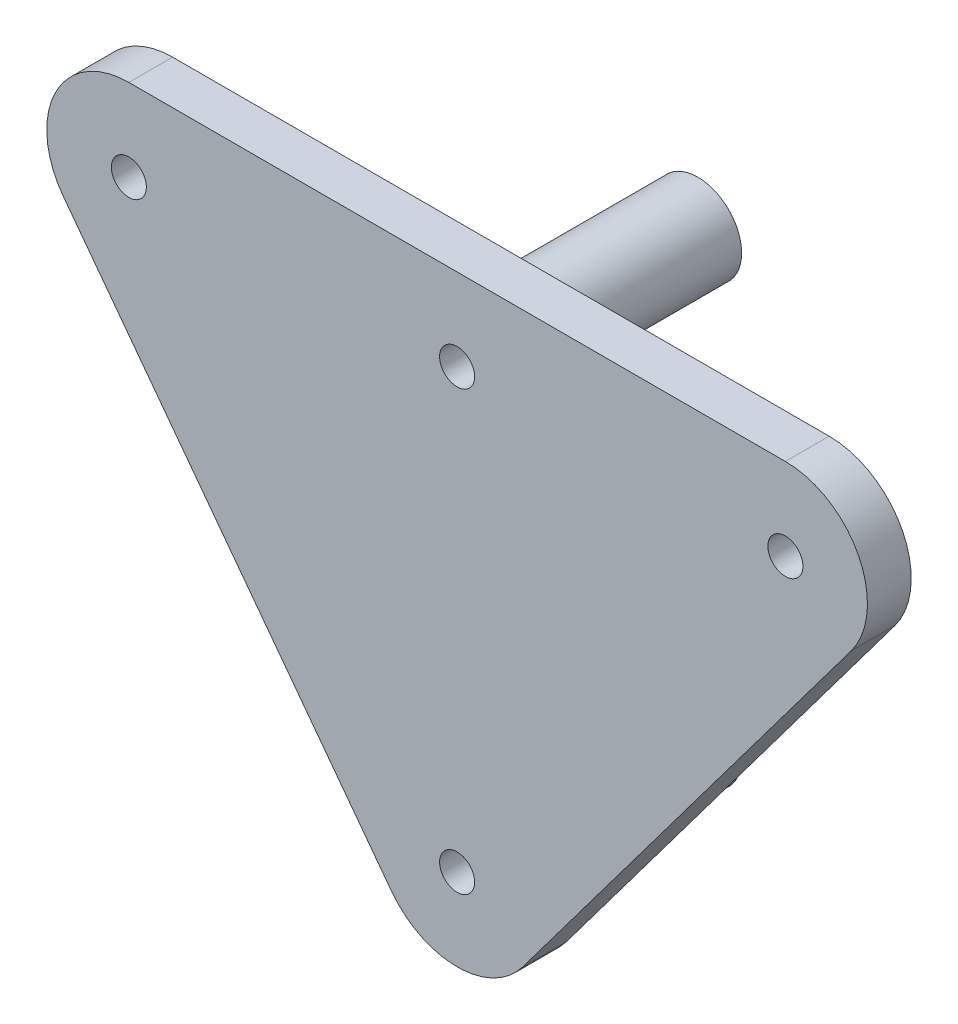
SolidWorks part; units mm, degrees
ref_plane "Front Plane" through (0, 0, 0) normal (0, 0, 1) x (1, 0, 0)
ref_plane "Top Plane" through (0, 0, 0) normal (0, 1, 0) x (1, 0, 0)
ref_plane "Right Plane" through (0, 0, 0) normal (1, 0, 0) x (0, 0, -1)
ref_axis "X" through (-88.99, 0, 0) along (1, 0, 0)
ref_axis "Y" through (0, 55, 0) along (0, -1, 0)
ref_axis "Z" through (0, 0, -88.99) along (0, 0, 1)
sketch "Sketch1" plane through (0, 0, 0) normal (0, 0, 1) x (1, 0, 0)
  line L0 (-36, 15.5) -> (-6, -24.5)
  line L1 (6, -24.5) -> (36, 15.5)
  line L2 (-30, 27.5) -> (30, 27.5)
  circle A0 centre (-30, 20) radius 7.5
  circle A1 centre (30, 20) radius 7.5
  circle A2 centre (0, -20) radius 7.5
  circle A3 centre (0, 20) radius 7.5
  circle A4 centre (0, 20) radius 4
  circle A5 centre (0, -20) radius 4
  circle A6 centre (-30, 20) radius 1.6
  circle A7 centre (0, 20) radius 1.6
  circle A8 centre (0, -20) radius 1.6
  circle A9 centre (30, 20) radius 1.6
  dimension "D1" = 15
  dimension "D2" = 8
  dimension "D3" = 3.2
extrude "Boss-Extrude1" add sketch "Sketch1" along normal blind 4 contours A0 | L2 A3 A0 L0 A2 L1 A1 | A1 | A2 A5 | A3 A4 | A4 | A5 region at (5.1533, 25.1533, 0) region at (0, 6.0857, 0) region at (-36.5185, 23.2592, 0) region at (-2.3046, -13.0861, 0) region at (23.4815, 16.7408, 0) region at (-3.8869, 20, 0) region at (-3.8869, -20, 0)
extrude "Boss-Extrude2" add sketch "Sketch1<4>" against normal up to surface (18 mm away) contours A4 A7 | A5 A8 region at (-3.8869, 20, 0) region at (-3.8869, -20, 0)
sketch "Sketch1<4>" plane through (0, 0, 0) normal (0, 0, 1) x (1, 0, 0) same geometry as "Sketch1"
sketch "Sketch3" plane through (0, 0, 0) normal (0, 0, -1) x (-1, 0, 0)
  circle A0 centre (30, 20) radius 1.6 construction
  circle A1 centre (-30, 20) radius 1.6 construction
  circle A2 centre (30, 20) radius 1.6
  circle A3 centre (-30, 20) radius 1.6
  circle A4 centre (-30, 20) radius 3.6
  circle A5 centre (30, 20) radius 3.6
  point P6 (0, 0)
  dimension "D1" = 2
extrude "Boss-Extrude3" add sketch "Sketch3" along normal blind 0.5
fillet "Fillet1" radius 2 2 edges at (4, -20, 0) (4, 20, 0)
